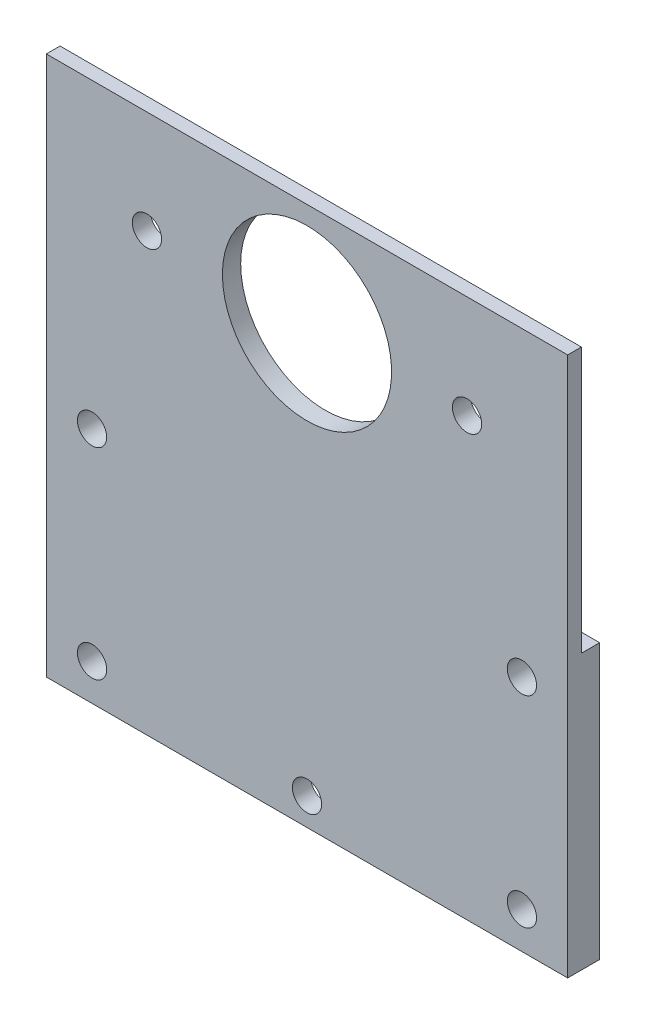
SolidWorks part; units mm, degrees
ref_plane "Ebene vorne" through (0, 0, 0) normal (0, 0, 1) x (1, 0, 0)
ref_plane "Ebene oben" through (0, 0, 0) normal (0, 1, 0) x (1, 0, 0)
ref_plane "Ebene rechts" through (0, 0, 0) normal (1, 0, 0) x (0, 0, -1)
sketch "Skizze1" plane through (0, 0, 0) normal (0, 0, 1) x (1, 0, 0)
  line L0 (0, 0) -> (0, 72.9146) construction
  line L1 (-28.5, 59) -> (28.5, 59)
  line L2 (28.5, 59) -> (28.5, 0)
  line L3 (28.5, 0) -> (-28.5, 0)
  line L4 (-28.5, 59) -> (-28.5, 0)
  point P7 (0, 59)
  dimension "D1" = 57
  dimension "D2" = 59
extrude "Grundkörper" add sketch "Skizze1" along normal blind 2
sketch "Skizze2" plane through (0, 0, 0) normal (0, 0, -1) x (-1, 0, 0)
  line L0 (0, 0) -> (0, 59.4137) construction
  line L1 (-18.082, 47.75) -> (18.082, 47.75) construction
  line L2 (-28.5, 59) -> (28.5, 59) construction
  circle A0 centre (0, 47.75) radius 9.25
  circle A1 centre (-17.5, 47.75) radius 1.6
  circle A2 centre (17.5, 47.75) radius 1.6
  dimension "D1" = 3.2
  dimension "D2" = 18.5
  dimension "D3" = 11.25
  dimension "D4" = 35
extrude "Bohrungen_Kugelroller" cut sketch "Skizze2" against normal through all
sketch "Skizze3" plane through (0, 0, 0) normal (0, 0, -1) x (-1, 0, 0)
  line L0 (0, 59) -> (0, -0.4438) construction
  line L1 (-28.5, 59) -> (28.5, 59) construction
  line L2 (-28.5, 30) -> (-18.5, 30)
  line L3 (-28.5, 0) -> (-28.5, 59) construction
  line L4 (-18.5, 30) -> (-18.5, 0)
  line L5 (28.5, 0) -> (18.5, 0)
  line L6 (28.5, 30) -> (28.5, 0)
  line L7 (-28.5, 30) -> (-28.5, 0)
  line L8 (-28.5, 0) -> (-18.5, 0)
  line L9 (28.5, 0) -> (-28.5, 0) construction
  line L10 (18.5, 30) -> (18.5, 0)
  line L11 (28.5, 30) -> (18.5, 30)
  dimension "D1" = 10
  dimension "D2" = 30
extrude "Aufsatz_Getriebehalter" add sketch "Skizze3" along normal blind 2
sketch "Skizze4" plane through (0, 0, -2) normal (0, 0, -1) x (-1, 0, 0)
  line L0 (0, 57.8388) -> (0, -14.2703) construction
  line L1 (24, 15) -> (-24, 15) construction
  line L2 (-23.5, 30) -> (-23.5, -0.0042) construction
  line L3 (24, 22.0317) -> (24, 7.9683) construction
  line L4 (-18.5, 15) -> (-29.1223, 15) construction
  line L5 (-18.5, 0) -> (-18.5, 30) construction
  line L7 (-18.5, 30) -> (-28.5, 30) construction
  circle A0 centre (-23.5, 26) radius 1.6
  circle A1 centre (23.5, 26) radius 1.6
  circle A2 centre (23.5, 4) radius 1.6
  circle A3 centre (-23.5, 4) radius 1.6
  point P10 (0, 15)
  dimension "D1" = 3.2
  dimension "D2" = 22
extrude "Bohrungen_Getriebehalter" cut sketch "Skizze4" against normal through all
sketch "Skizze5" plane through (0, 0, 0) normal (0, 0, -1) x (-1, 0, 0)
  line L0 (0, 61.2734) -> (0, -5.0948) construction
  line L1 (18.5, 0) -> (-18.5, 0) construction
  circle A0 centre (0, 3) radius 1.6
  dimension "D1" = 3.2
  dimension "D2" = 3
extrude "Bohrung_Halterung" cut sketch "Skizze5" against normal through all
sketch "Skizze8" plane through (0, 0, 0) normal (0, 0, -1) x (-1, 0, 0)
  line L0 (-16.5, 13) -> (-16.5, 3)
  line L1 (-16.5, 3) -> (-4, 3)
  line L2 (-4, 3) -> (-4, 7.5)
  line L3 (-4, 7.5) -> (-16.5, 13)
  line L4 (-4, 9.5) -> (-4, 20.5)
  line L5 (-4, 20.5) -> (-16.5, 15)
  line L6 (-16.5, 15) -> (-4, 9.5)
  line L7 (-16.5, 28) -> (-16.5, 17)
  line L8 (-16.5, 17) -> (-4, 22.5)
  line L9 (-4, 22.5) -> (-16.5, 28)
  line L10 (-16.5, 30) -> (-4, 24.5)
  line L11 (-4, 24.5) -> (-4, 35.5)
  line L12 (-4, 35.5) -> (-16.5, 30)
  line L13 (0, 0) -> (0, 65.3922) construction
  line L14 (-26.178, 32) -> (-16.5, 32)
  line L15 (-16.5, 32) -> (-4, 37.5)
  line L16 (-18.5, 0) -> (-18.5, 30) construction
  line L17 (18.5, 0) -> (-18.5, 0) construction
  line L18 (-4, 37.5) -> (-26.178, 37.5)
  line L19 (-26.178, 37.5) -> (-26.178, 32)
  line L20 (-18.5, 30) -> (-28.5, 30) construction
  line L21 (26.178, 37.5) -> (26.178, 32)
  line L22 (4, 37.5) -> (26.178, 37.5)
  line L23 (16.5, 32) -> (4, 37.5)
  line L24 (26.178, 32) -> (16.5, 32)
  line L25 (4, 35.5) -> (16.5, 30)
  line L26 (4, 24.5) -> (4, 35.5)
  line L27 (16.5, 30) -> (4, 24.5)
  line L28 (4, 22.5) -> (16.5, 28)
  line L29 (16.5, 17) -> (4, 22.5)
  line L30 (16.5, 28) -> (16.5, 17)
  line L31 (16.5, 15) -> (4, 9.5)
  line L32 (4, 20.5) -> (16.5, 15)
  line L33 (4, 9.5) -> (4, 20.5)
  line L34 (4, 7.5) -> (16.5, 13)
  line L35 (4, 3) -> (4, 7.5)
  line L36 (16.5, 3) -> (4, 3)
  line L37 (16.5, 13) -> (16.5, 3)
  dimension "D1" = 2
  dimension "D2" = 4
  dimension "D3" = 3
  dimension "D4" = 10
  dimension "D5" = 2
  dimension "D6" = 2
  dimension "D7" = 2
  dimension "D8" = 11
  dimension "D9" = 2
extrude "Schnitt-Linear austragen4" cut sketch "Skizze8" against normal blind 1
fillet "Verrundung_Ausschnitte" radius 1 34 edges at (-26.178, 34.75, 1) (-21.339, 32, 1) (-10.25, 34.75, 1) (-15.089, 37.5, 1) (-10.25, 32.75, 1) (-10.25, 27.25, 1) (-4, 30, 1) (-10.25, 25.25, 1) (-16.5, 22.5, 1) (-10.25, 19.75, 1) (-10.25, 12.25, 1) (-4, 15, 1) (-10.25, 17.75, 1) (-10.25, 10.25, 1) (-16.5, 8, 1) (-10.25, 3, 1) (-4, 5.25, 1) (4, 5.25, 1) (10.25, 3, 1) (16.5, 8, 1) (10.25, 10.25, 1) (10.25, 17.75, 1) (4, 15, 1) (10.25, 12.25, 1) (10.25, 19.75, 1) (16.5, 22.5, 1) (10.25, 25.25, 1) (4, 30, 1) (10.25, 27.25, 1) (10.25, 32.75, 1) (10.25, 34.75, 1) (21.339, 32, 1) (26.178, 34.75, 1) (15.089, 37.5, 1)
fillet "Verrundung4" radius 1 34 edges at (5.3929, 37.2071, 0.7071) (4.2929, 3.2929, 0.7071) (16.2071, 3.2929, 0.7071) (4.2929, 9.9489, 0.7071) (15.7727, 15, 0.7071) (4.2929, 7.3089, 0.7071) (16.2071, 12.5511, 0.7071) (4.2929, 20.0511, 0.7071) (4.7273, 22.5, 0.7071) (16.2071, 17.4489, 0.7071) (16.2071, 27.5511, 0.7071) (4.2929, 35.0511, 0.7071) (4.2929, 24.9489, 0.7071) (15.7727, 30, 0.7071) (16.5616, 32.2929, 0.7071) (25.8851, 32.2929, 0.7071) (25.8851, 37.2071, 0.7071) (-16.2071, 3.2929, 0.7071) (-16.2071, 12.5511, 0.7071) (-4.2929, 3.2929, 0.7071) (-4.2929, 7.3089, 0.7071) (-4.2929, 20.0511, 0.7071) (-4.2929, 9.9489, 0.7071) (-15.7727, 15, 0.7071) (-16.2071, 17.4489, 0.7071) (-16.2071, 27.5511, 0.7071) (-4.7273, 22.5, 0.7071) (-15.7727, 30, 0.7071) (-4.2929, 35.0511, 0.7071) (-4.2929, 24.9489, 0.7071) (-5.3929, 37.2071, 0.7071) (-16.5616, 32.2929, 0.7071) (-25.8851, 37.2071, 0.7071) (-25.8851, 32.2929, 0.7071)
chamfer "Fase1" distance 0.5 angle 45 12 edges at (0, 0, 0) (-28.5, 44.5, 0) (28.5, 44.5, 0) (0, 59, 0) (28.5, 15, -2) (23.5, 0, -2) (23.5, 30, -2) (18.5, 15, -2) (-28.5, 15, -2) (-23.5, 0, -2) (-18.5, 15, -2) (-23.5, 30, -2)
